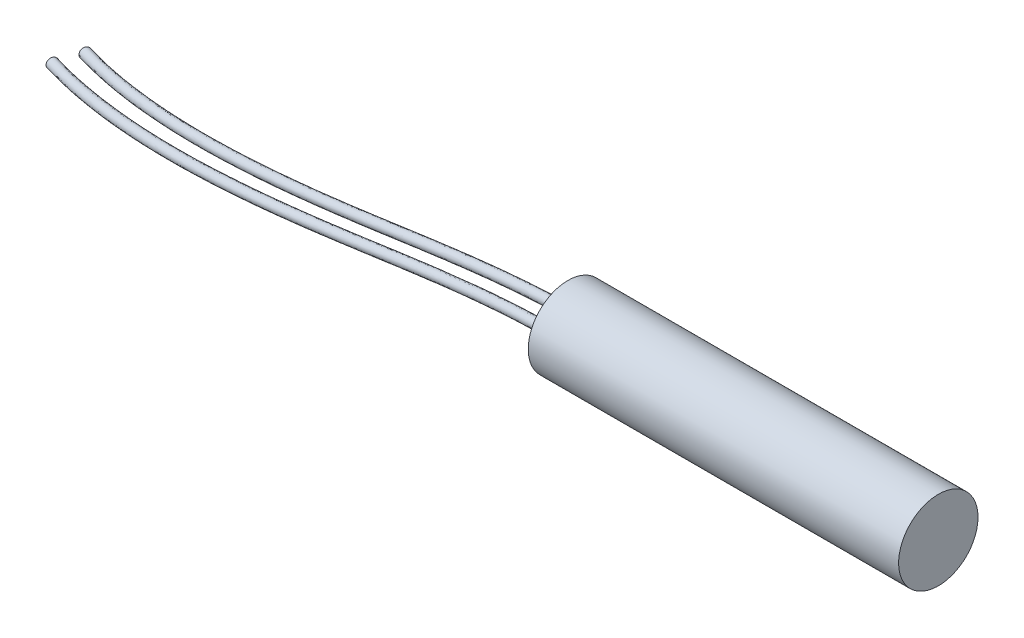
SolidWorks part; units mm, degrees
ref_plane "Front" through (0, 0, 0) normal (0, 0, 1) x (1, 0, 0)
ref_plane "Top" through (0, 0, 0) normal (0, 1, 0) x (1, 0, 0)
ref_plane "Right" through (0, 0, 0) normal (1, 0, 0) x (0, 0, -1)
sketch "Sketch1" plane through (0, 0, 0) normal (1, 0, 0) x (0, 0, -1)
  circle A0 centre (0, 0) radius 3
  dimension "D1" = 6
extrude "Boss-Extrude1" add sketch "Sketch1" along normal blind 28
sketch "Sketch2" plane through (0, 0, 0) normal (0, 1, 0) x (1, 0, 0)
  line L0 (0, 0) -> (-8.4805, 0) construction
  spline S0 degree 3 poles (0, 0) (-5.8116, 0) (-16.7933, -2.4118) (-29.753, -3.2995) (-36.4364, -1.3057) knots 0 0 0 0 0.427107 1 1 1 1
sketch "Sketch3" plane through (0, 0, 0) normal (-1, 0, 0) x (0, 0, 1)
  line L0 (0, 0) -> (-1, 0) construction
  line L1 (0, 0) -> (0, 1.1308) construction
  circle A0 centre (-1, 0) radius 0.375
  circle A2 centre (1, 0) radius 0.375
  dimension "D1" = 1
  dimension "D2" = 0.75
sweep "Sweep1" add profiles "Sketch3" path "Sketch2"
